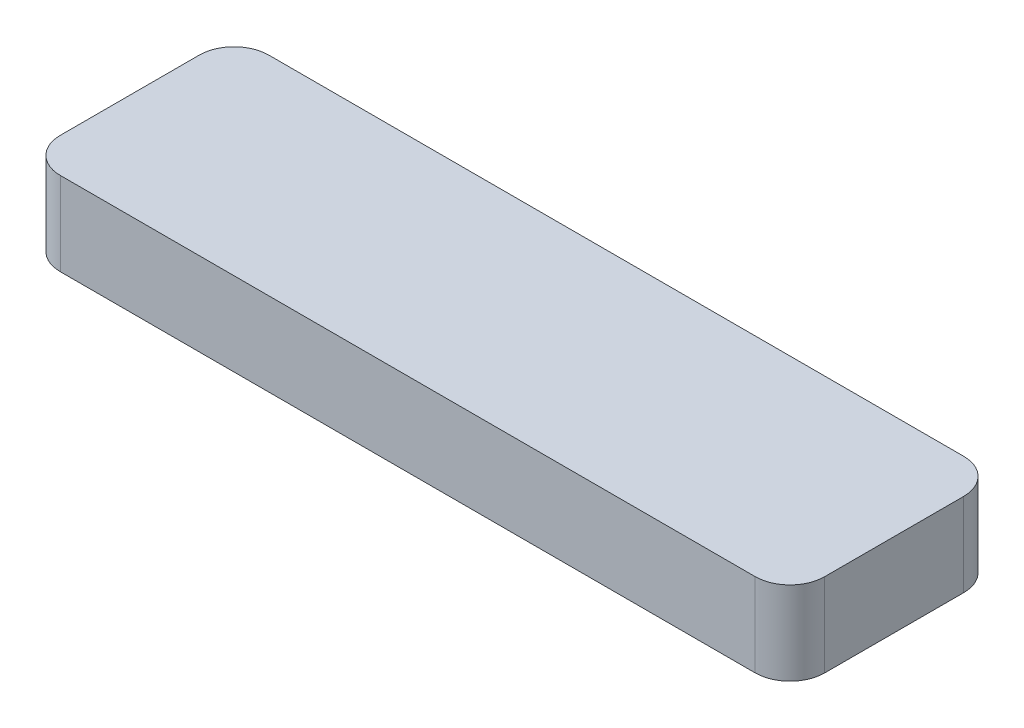
SolidWorks part; units mm, degrees
ref_plane "Front Plane" through (0, 0, 0) normal (0, 0, 1) x (1, 0, 0)
ref_plane "Top Plane" through (0, 0, 0) normal (0, 1, 0) x (1, 0, 0)
ref_plane "Right Plane" through (0, 0, 0) normal (1, 0, 0) x (0, 0, -1)
sketch "Sketch1" plane through (0, 0, 0) normal (0, 1, 0) x (1, 0, 0)
  line L1 (-49.6146, 18.5384) -> (60.3854, 18.5384)
  line L2 (-49.6146, 18.5384) -> (-49.6146, -11.4616)
  line L3 (-49.6146, -11.4616) -> (60.3854, -11.4616)
  line L4 (60.3854, 18.5384) -> (60.3854, -11.4616)
  dimension "D1" = 110
  dimension "D2" = 30
extrude "Boss-Extrude1" add sketch "Sketch1" along normal blind 12
ref_plane "Plane1" through (0, -1, 0) normal (0, -1, 0) x (-1, 0, 0)
sketch "Sketch2" plane through (0, -1, 0) normal (0, -1, 0) x (-1, 0, 0)
  line L0 (-60.3854, 3.5384) -> (57.5711, 3.5384) construction
  line L1 (-41.1646, 0.6384) -> (-44.5646, 0.6384)
  line L2 (-41.1646, 0.6384) -> (-41.1646, 6.4384)
  line L3 (-41.1646, 6.4384) -> (-44.5646, 6.4384)
  line L4 (-44.5646, 0.6384) -> (-44.5646, 6.4384)
  line L5 (-60.3854, -11.4616) -> (-60.3854, 18.5384) construction
  line L6 (-42.8646, -11.4616) -> (-42.8646, 27.765) construction
  line L8 (49.6146, -11.4616) -> (-60.3854, -11.4616) construction
  dimension "D1" = 3.4
  dimension "D2" = 5.8
  dimension "D3" = 1.7
  dimension "D4" = 2.9
extrude "Boss-Extrude2" add sketch "Sketch2" along normal blind 6 separate body
shell "Shell1" thickness 1 removed face at (42.8646, -7, -3.5384) outward yes
sketch "Sketch3" plane through (0, 0, 0) normal (0, -1, 0) x (-1, 0, 0)
  line L0 (-42.8646, 0.6384) -> (-42.8646, 11.0227) construction
  line L1 (-44.5646, 0.6384) -> (-41.1646, 0.6384) construction
  line L2 (-41.1646, 3.5384) -> (-49.8164, 3.5384) construction
  line L3 (-41.1646, 0.6384) -> (-41.1646, 6.4384) construction
  point P8 (0, 0)
  point P9 (-42.8646, 3.5384)
  point P10 (0, 0)
sketch "Sketch4" plane through (0, 0, 0) normal (0, -1, 0) x (-1, 0, 0)
  circle A0 centre (-42.9099, 3.5376) radius 4.5
  circle A1 centre (-42.9099, 3.5376) radius 3.7
extrude "Boss-Extrude3" add sketch "Sketch4" along normal blind 9
sketch "Sketch5" plane through (0, 0, 0) normal (0, -1, 0) x (-1, 0, 0)
  circle A0 centre (-42.8646, 3.5384) radius 4.25
  circle A1 centre (-42.8646, 3.5384) radius 5.5
extrude "Boss-Extrude4" add sketch "Sketch5" along normal blind 4
fillet "Fillet1" radius 5 4 edges at (-49.6146, 6, -18.5384) (-49.6146, 6, 11.4616) (60.3854, 6, -18.5384) (60.3854, 6, 11.4616)
